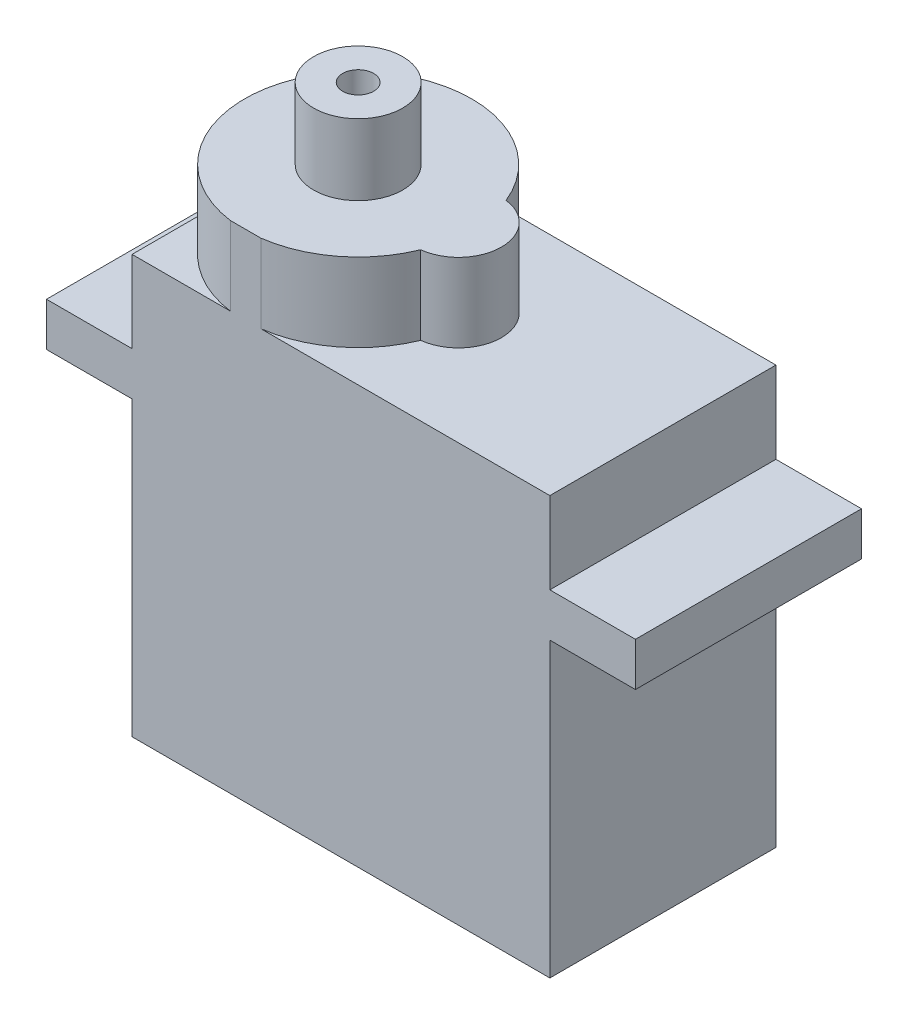
SolidWorks part; units mm, degrees
ref_plane "Front Plane" through (0, 0, 0) normal (0, 0, 1) x (1, 0, 0)
ref_plane "Top Plane" through (0, 0, 0) normal (0, 1, 0) x (1, 0, 0)
ref_plane "Right Plane" through (0, 0, 0) normal (1, 0, 0) x (0, 0, -1)
sketch "Sketch1" plane through (0, 0, 0) normal (0, 0, 1) x (1, 0, 0)
  line L1 (-16.7887, 19.3155) -> (5.5713, 19.3155)
  line L2 (-16.7887, 19.3155) -> (-16.7887, -3.0445)
  line L3 (-16.7887, -3.0445) -> (5.5713, -3.0445)
  line L4 (5.5713, 19.3155) -> (5.5713, -3.0445)
  dimension "D1" = 22.36
  dimension "D2" = 22.36
extrude "Boss-Extrude1" add sketch "Sketch1" along normal blind 12.1
sketch "Sketch2" plane through (5.5713, 0, 0) normal (1, 0, 0) x (0, 0, -1)
  line L0 (-12.1, -3.0445) -> (-12.1, 19.3155) construction
  line L1 (-12.1, 14.9455) -> (0, 14.9455)
  line L2 (-12.1, 14.9455) -> (-12.1, 12.6155)
  line L3 (-12.1, 12.6155) -> (0, 12.6155)
  line L4 (0, 14.9455) -> (0, 12.6155)
  line L5 (0, -3.0445) -> (0, 19.3155) construction
  line L7 (-12.1, 19.3155) -> (0, 19.3155) construction
  dimension "D1" = 6.7
  dimension "D2" = 2.33
extrude "Boss-Extrude2" add sketch "Sketch2" along normal blind 4.58
sketch "Sketch5" plane through (-16.7887, 0, 0) normal (-1, 0, 0) x (0, 0, 1)
  line L0 (0, 19.3155) -> (0, -3.0445) construction
  line L1 (0, 14.9455) -> (12.1, 14.9455)
  line L2 (0, 14.9455) -> (0, 12.6155)
  line L3 (0, 12.6155) -> (12.1, 12.6155)
  line L4 (12.1, 14.9455) -> (12.1, 12.6155)
  line L5 (12.1, 19.3155) -> (12.1, -3.0445) construction
  line L6 (12.1, 19.3155) -> (0, 19.3155) construction
  dimension "D1" = 6.7
  dimension "D2" = 2.33
extrude "Boss-Extrude5" add sketch "Sketch5" along normal blind 4.58
sketch "Sketch7" plane through (0, 19.3155, 0) normal (0, 1, 0) x (1, 0, 0)
  line L0 (-16.7887, -12.1) -> (-16.7887, 0) construction
  line L1 (5.5713, 0) -> (-16.7887, 0) construction
  circle A0 centre (-10.7113, -6.0773) radius 6.0773
  arc A1 (-5.0799, -8.3624) -> (-5.0799, -3.7923) centre (-5.3415, -6.0773) ccw
  line M6 (-16.7887, -12.1) -> (5.5713, -12.1)
extrude "Boss-Extrude6" add sketch "Sketch7" along normal blind 4.2 contours A0 M6 | A0 A1 region at (-10.7113, 19.3155, 6.0742) region at (-4.0608, 19.3155, 6.0773)
sketch "Sketch8" plane through (0, 23.5155, 0) normal (0, 1, 0) x (1, 0, 0)
  line L1 (-11.5247, -12.1) -> (-9.8979, -12.1)
  line L2 (-11.5247, -12.1) -> (-9.8979, -12.1)
  circle A0 centre (-10.7113, -6.0773) radius 2.385
  arc A3 (-9.8979, -12.1) -> (-5.0799, -8.3624) centre (-10.7113, -6.0773) ccw
  arc A4 (-5.0799, -8.3624) -> (-5.0799, -3.7923) centre (-5.3415, -6.0773) ccw
  arc A5 (-5.0799, -3.7923) -> (-11.5247, -12.1) centre (-10.7113, -6.0773) ccw
  arc A6 (-9.8979, -12.1) -> (-5.0799, -8.3624) centre (-10.7113, -6.0773) ccw
  arc A7 (-5.0799, -8.3624) -> (-5.0799, -3.7923) centre (-5.3415, -6.0773) ccw
  arc A8 (-5.0799, -3.7923) -> (-11.5247, -12.1) centre (-10.7113, -6.0773) ccw
  dimension "D1" = 0
extrude "Boss-Extrude7" add sketch "Sketch8" along normal blind 3.8 contours A0 region at (-10.7113, 23.5155, 6.0773)
sketch "Sketch9" plane through (0, 27.3155, 0) normal (0, 1, 0) x (1, 0, 0)
  circle A0 centre (-10.7113, -6.0773) radius 0.83
  circle A1 centre (-10.7113, -6.0773) radius 2.385
  circle A2 centre (-10.7113, -6.0773) radius 2.385
  dimension "D1" = 0
extrude "Cut-Extrude1" cut sketch "Sketch9" against normal blind 4.05 contours A0 region at (-10.7113, 27.3155, 6.0773)
